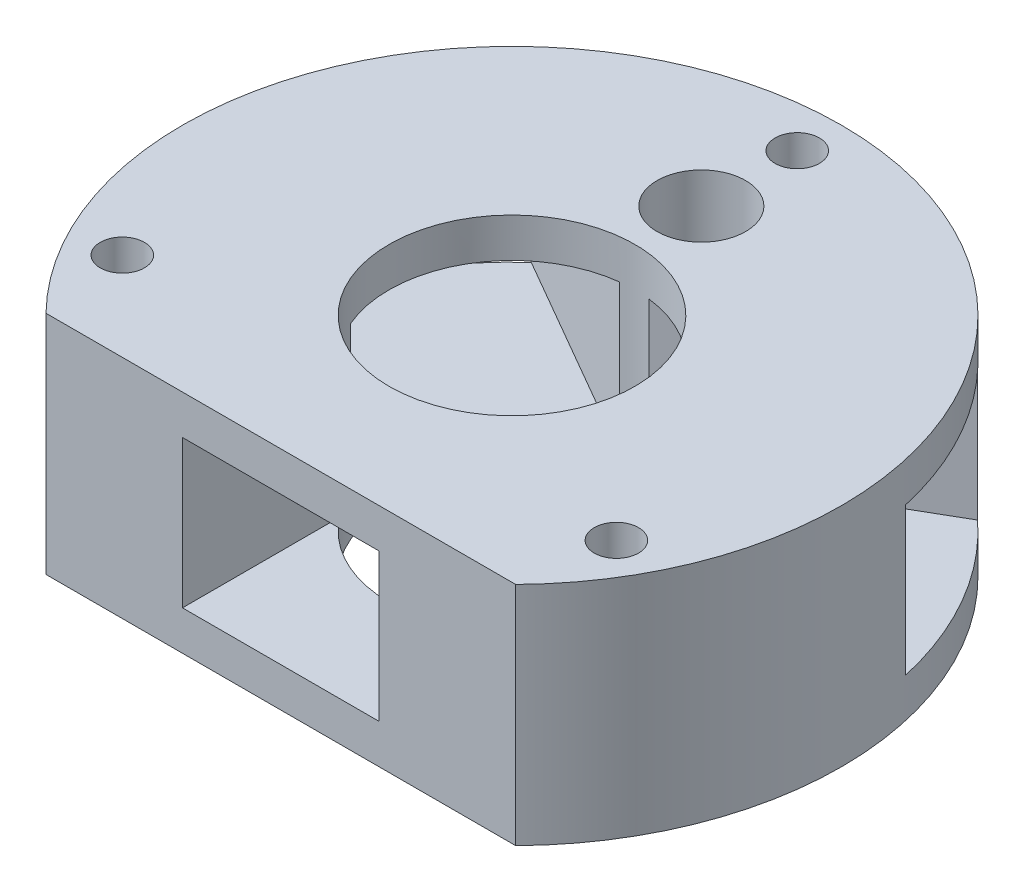
SolidWorks part; units mm, degrees
note: '?' marks a value the reader was unsure of.
ref_plane "前视基准面" through (0, 0, 0) normal (0, 0, 1) x (1, 0, 0)
ref_plane "上视基准面" through (0, 0, 0) normal (0, 1, 0) x (1, 0, 0)
ref_plane "右视基准面" through (0, 0, 0) normal (1, 0, 0) x (0, 0, -1)
sketch "草图1" plane through (0, 0, 0) normal (0, 1, 0) x (1, 0, 0)
  circle A0 centre (0, 0) radius 33.5
  dimension "D1" = 67
extrude "凸台-拉伸1" add sketch "草图1" along normal blind 23
sketch "草图2" plane through (0, 23, 0) normal (0, 1, 0) x (1, 0, 0)
  line L0 (0, 0) -> (0, 29)
  line L1 (0, 0) -> (-25.1147, -14.5)
  line L2 (0, 0) -> (25.1147, -14.5)
  circle A0 centre (0, 0) radius 29
  circle A1 centre (0, 0) radius 19.25
  dimension "D1" = 58
  dimension "D4" = 38.5
  dimension "D2" = 120
  dimension "D3" = 120
sketch "草图3" plane through (0, 23, 0) normal (0, 1, 0) x (1, 0, 0)
  point P0 (0, 29)
  point P3 (-25.1147, -14.5)
  point P6 (25.1147, -14.5)
hole_wizard "孔1" positions "草图3" profile "草图4" legacy end condition up to next
sketch "草图4" plane through (0, 23, -29) normal (1, 0, 0) x (0, 0, 1)
  line L0 (0, 0) -> (0, 23)
  line L1 (0, 23) -> (2.25, 23)
  line L2 (2.25, 23) -> (2.25, 0)
  line L3 (2.25, 0) -> (0, 0)
  line L4 (0, 110) -> (0, -10) construction
  dimension "直径" = 4.5
  dimension "深度" = 23
sketch "草图5" plane through (0, 23, 0) normal (0, 1, 0) x (1, 0, 0)
  line L0 (0, 0) -> (0, 29) construction
  circle A0 centre (0, 0) radius 19.25 construction
  point P0 (0, 19.25)
hole_wizard "孔2" positions "草图5" profile "草图6" legacy end condition up to next
sketch "草图6" plane through (0, 23, -19.25) normal (1, 0, 0) x (0, 0, 1)
  line L0 (0, 0) -> (0, 23)
  line L1 (0, 23) -> (4.5, 23)
  line L2 (4.5, 23) -> (4.5, 0)
  line L3 (4.5, 0) -> (0, 0)
  line L4 (0, 110) -> (0, -10) construction
  dimension "直径" = 9
  dimension "深度" = 23
hole_wizard "孔3" positions "草图7" profile "草图8" legacy end condition up to next
sketch "草图7" plane through (0, 23, 0) normal (0, 1, 0) x (1, 0, 0)
  point P0 (0, 0)
sketch "草图8" plane through (0, 23, 0) normal (1, 0, 0) x (0, 0, 1)
  line L0 (0, 0) -> (0, 23)
  line L1 (0, 23) -> (12.5, 23)
  line L2 (12.5, 23) -> (12.5, 0)
  line L3 (12.5, 0) -> (0, 0)
  line L4 (0, 110) -> (0, -10) construction
  dimension "直径" = 25
  dimension "深度" = 23
ref_plane "基准面4" through (0, 0, 33.5) normal (0, 0, 1) x (1, 0, 0)
sketch "草图9" plane through (0, 0, 33.5) normal (0, 0, 1) x (1, 0, 0)
  line L0 (0, 23) -> (0, 0)
  line L1 (19.25, 23) -> (-19.25, 23) construction
  line L3 (-10, 4) -> (10, 4)
  line L4 (-10, 4) -> (-10, 19)
  line L5 (-10, 19) -> (10, 19)
  line L6 (10, 4) -> (10, 19)
  line L7 (-10, 4) -> (10, 19) construction
  line L8 (-10, 19) -> (10, 4) construction
  point P5 (0, 11.5)
  dimension "D1" = 15
  dimension "D2" = 20
extrude "切除-拉伸1" cut sketch "草图9" against normal blind 30 contours L3 L6 L5 L0 | L5 L4 L3 L0
ref_axis "基准轴1" through (0, 23, 0) along (0, 1, 0)?
pattern_circular "阵列(圆周)1" count 3 every 120 about axis through (0, 0, 0) along (0, 1, 0) of "切除-拉伸1"
sketch "草图10" plane through (0, 0, 33.5) normal (0, 0, 1) x (1, 0, 0)
  line L1 (-33.5, 0) -> (33.5, 0)
  line L2 (-33.5, 0) -> (-33.5, 23)
  line L3 (-33.5, 23) -> (33.5, 23)
  line L4 (33.5, 0) -> (33.5, 23)
extrude "切除-拉伸2" cut sketch "草图10" against normal blind 10
